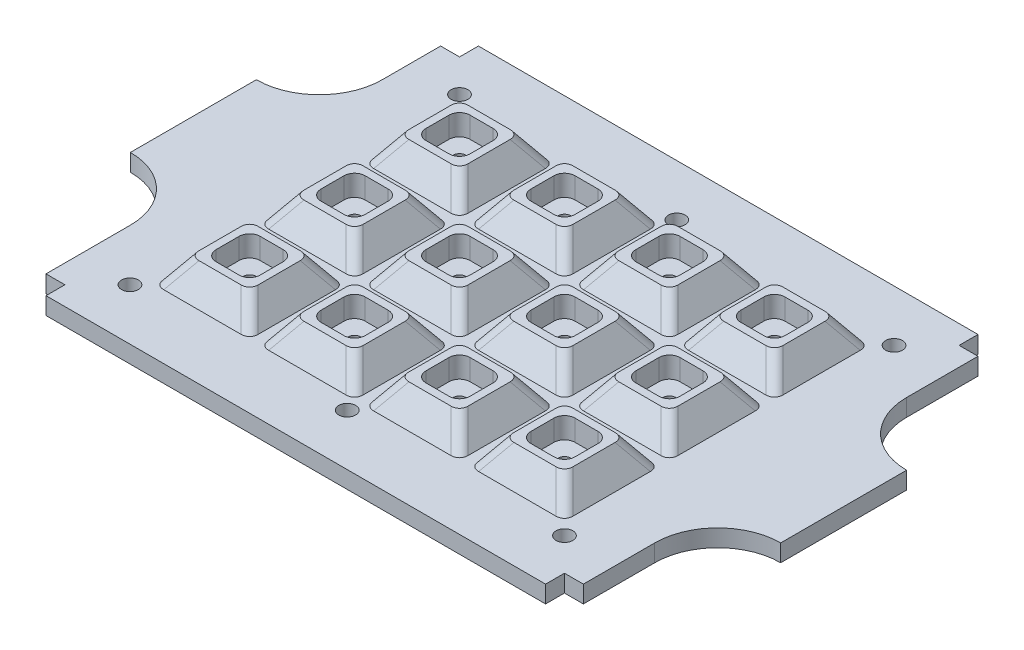
SolidWorks part; units mm, degrees
ref_plane "Front Plane" through (0, 0, 0) normal (0, 0, 1) x (1, 0, 0)
ref_plane "Top Plane" through (0, 0, 0) normal (0, 1, 0) x (1, 0, 0)
ref_plane "Right Plane" through (0, 0, 0) normal (1, 0, 0) x (0, 0, -1)
sketch "Sketch1" plane through (0, 0, 0) normal (0, 1, 0) x (1, 0, 0)
  line L1 (0, 0) -> (31.75, 0)
  line L2 (0, 0) -> (0, 31.75)
  line L3 (0, 31.75) -> (31.75, 31.75)
  line L4 (31.75, 0) -> (31.75, 31.75)
  dimension "D1" = 31.75
extrude "Boss-Extrude1" add sketch "Sketch1" along normal blind 2.0828
sketch "Sketch2" plane through (0, 2.0828, 0) normal (0, 1, 0) x (1, 0, 0)
  line L0 (21.59, 15.875) -> (31.75, 15.875) construction
  line L1 (10.16, 21.59) -> (21.59, 21.59)
  line L2 (10.16, 21.59) -> (10.16, 10.16)
  line L3 (10.16, 10.16) -> (21.59, 10.16)
  line L4 (21.59, 21.59) -> (21.59, 10.16)
  line L5 (31.75, 0) -> (31.75, 31.75) construction
  line L6 (15.875, 10.16) -> (15.875, 0) construction
  line L7 (0, 0) -> (31.75, 0) construction
  dimension "D1" = 11.43
extrude "Boss-Extrude2" add sketch "Sketch2" along normal blind 3.048 draft 35 contours L4 L3 L2 L1
sketch "Sketch3" plane through (0, 5.1308, 0) normal (0, 1, 0) x (1, 0, 0)
  line L0 (15.875, 18.542) -> (15.875, 21.59) construction
  line L1 (13.208, 18.542) -> (18.542, 18.542)
  line L2 (13.208, 18.542) -> (13.208, 13.208)
  line L3 (13.208, 13.208) -> (18.542, 13.208)
  line L4 (18.542, 18.542) -> (18.542, 13.208)
  line L5 (10.16, 21.59) -> (21.59, 21.59) construction
  line L6 (18.542, 15.875) -> (19.4558, 15.875) construction
  line L7 (19.4558, 19.4558) -> (19.4558, 12.2942) construction
  line L8 (18.542, 15.875) -> (19.4558, 15.875) construction
  dimension "D1" = 5.334
extrude "Cut-Extrude1" cut sketch "Sketch3" against normal blind 2.54
fillet "Fillet4" radius 1.27 4 edges at (13.208, 3.8608, -18.542) (13.208, 3.8608, -13.208) (18.542, 3.8608, -13.208) (18.542, 3.8608, -18.542)
sketch "Sketch4" plane through (0, 2.0828, 0) normal (0, 1, 0) x (1, 0, 0)
  line L0 (10.16, 21.59) -> (10.16, 31.75) construction
  line L1 (31.75, 31.75) -> (0, 31.75) construction
  line L2 (10.16, 10.16) -> (0, 10.16) construction
  line L3 (0, 31.75) -> (0, 0) construction
  line L6 (15.875, 31.75) -> (15.875, 0) construction
  line L7 (0, 0) -> (31.75, 0) construction
  line L8 (0, 15.875) -> (31.75, 15.875) construction
  line L9 (31.75, 0) -> (31.75, 31.75) construction
  line L10 (4.9361, 26.8139) -> (10.16, 21.59) construction
  circle A0 centre (4.9361, 26.8139) radius 1.524
  circle A1 centre (26.8139, 26.8139) radius 1.524
  circle A2 centre (26.8139, 4.9361) radius 1.524
  circle A3 centre (4.9361, 4.9361) radius 1.524
  dimension "D1" = 3.048
extrude "Cut-Extrude2" cut sketch "Sketch4" against normal through all
sketch "Sketch6" plane through (0, 2.0828, 0) normal (0, 1, 0) x (1, 0, 0)
  line L0 (15.875, 13.208) -> (15.875, 18.542) construction
  line L1 (0, 0) -> (2.286, 0)
  line L2 (0, 0) -> (0, 2.286)
  line L3 (0, 2.286) -> (2.286, 2.286)
  line L4 (2.286, 0) -> (2.286, 2.286)
  line L5 (14.478, 13.208) -> (17.272, 13.208) construction
  line L6 (17.272, 18.542) -> (14.478, 18.542) construction
  line L7 (13.208, 15.875) -> (18.542, 15.875) construction
  line L8 (13.208, 17.272) -> (13.208, 14.478) construction
  line L9 (18.542, 14.478) -> (18.542, 17.272) construction
  line L10 (31.75, 2.286) -> (29.464, 2.286)
  line L11 (29.464, 0) -> (29.464, 2.286)
  line L12 (31.75, 0) -> (29.464, 0)
  line L13 (31.75, 0) -> (31.75, 2.286)
  line L14 (0, 31.75) -> (2.286, 31.75)
  line L15 (0, 31.75) -> (0, 29.464)
  line L16 (0, 29.464) -> (2.286, 29.464)
  line L17 (2.286, 31.75) -> (2.286, 29.464)
  line L18 (31.75, 31.75) -> (31.75, 29.464)
  line L19 (31.75, 31.75) -> (29.464, 31.75)
  line L20 (29.464, 31.75) -> (29.464, 29.464)
  line L21 (31.75, 29.464) -> (29.464, 29.464)
  line L22 (31.75, 0) -> (29.464, 0)
  line L23 (31.75, 0) -> (31.75, 2.286)
  line L24 (31.75, 2.286) -> (29.464, 2.286)
  line L25 (29.464, 0) -> (29.464, 2.286)
  point P21 (15.875, 15.875)
  point P37 (15.875, 15.875)
  line M22 (0, 31.75) -> (0, 0)
  line M23 (0, 0) -> (31.75, 0)
  line M24 (31.75, 0) -> (31.75, 31.75)
  line M25 (31.75, 31.75) -> (0, 31.75)
  dimension "D1" = 2.286
  dimension "D2" = 4
extrude "Cut-Extrude3" cut sketch "Sketch6" against normal through all contours L17 L16 M25 M22 | L4 L3 M23 M22 | L21 L20 M24 M25 | L11 L10 L13 L12 region at (1.143, 2.0828, -1.143) region at (1.143, 2.0828, -30.607) region at (30.607, 2.0828, -30.607)
fillet "Fillet1" radius 1.27 4 edges at (11.2271, 3.6068, -11.2271) (20.5229, 3.6068, -11.2271) (20.5229, 3.6068, -20.5229) (11.2271, 3.6068, -20.5229)
sketch "Sketch7" plane through (0, 0, 0) normal (0, -1, 0) x (1, 0, 0)
  line L0 (15.875, 0) -> (15.875, -31.75) construction
  line L1 (2.286, 0) -> (29.464, 0) construction
  line L2 (29.464, -31.75) -> (2.286, -31.75) construction
  line L4 (22.225, -22.225) -> (9.525, -22.225)
  line L5 (22.225, -22.225) -> (22.225, -9.525)
  line L6 (22.225, -9.525) -> (9.525, -9.525)
  line L7 (9.525, -22.225) -> (9.525, -9.525)
  line L8 (22.225, -22.225) -> (9.525, -9.525) construction
  line L9 (22.225, -9.525) -> (9.525, -22.225) construction
  line L10 (31.75, -31.75) -> (0, -31.75)
  line L11 (31.75, -31.75) -> (31.75, 0)
  line L12 (31.75, 0) -> (0, 0)
  line L13 (0, -31.75) -> (0, 0)
  line L14 (31.75, -31.75) -> (0, 0) construction
  line L15 (31.75, 0) -> (0, -31.75) construction
  point P6 (15.875, -15.875)
  point P11 (15.875, -15.875)
  dimension "D1" = 12.7
extrude "Cut-Extrude4" cut sketch "Sketch7" against normal blind 2.54
pattern_linear "LPattern1" count 4 spacing 12.7 along (1, 0, 0) count 3 spacing 12.7 along (0, 0, -1) of bodies 107
ref_plane "Plane1" through (34.925, 0, 0) normal (-1, 0, 0) x (0, 0, 1)
sketch "Sketch8" plane through (0, 0, 0) normal (0, -1, 0) x (1, 0, 0)
  line L0 (2.413, -28.575) -> (9.525, -28.575) construction
  line L1 (2.413, -2.413) -> (67.437, -2.413)
  line L2 (2.413, -2.413) -> (2.413, -54.737)
  line L3 (2.413, -54.737) -> (67.437, -54.737)
  line L4 (67.437, -2.413) -> (67.437, -54.737)
  line L5 (9.525, -22.225) -> (9.525, -34.925) construction
  line L6 (34.925, -9.525) -> (34.925, -54.737) construction
  line L8 (10.033, -37.7702) -> (-5.207, -37.7702)
  line L9 (10.033, -37.7702) -> (10.033, -22.5302)
  line L10 (10.033, -22.5302) -> (-5.207, -22.5302)
  line L11 (-5.207, -37.7702) -> (-5.207, -22.5302)
  line L12 (10.033, -37.7702) -> (-5.207, -22.5302) construction
  line L13 (10.033, -22.5302) -> (-5.207, -37.7702) construction
  line L14 (59.817, -36.195) -> (75.057, -36.195)
  line L15 (59.817, -36.195) -> (59.817, -20.955)
  line L16 (59.817, -20.955) -> (75.057, -20.955)
  line L17 (75.057, -36.195) -> (75.057, -20.955)
  line L18 (59.817, -36.195) -> (75.057, -20.955) construction
  line L19 (59.817, -20.955) -> (75.057, -36.195) construction
  point P11 (2.413, -30.1502)
  point P16 (67.437, -28.575)
  line M5 (47.625, -9.525) -> (34.925, -9.525)
  line M6 (34.925, -9.525) -> (34.925, -22.225)
  line M7 (34.925, -22.225) -> (47.625, -22.225)
  line M8 (47.625, -22.225) -> (47.625, -9.525)
  dimension "D1" = 65.024
  dimension "D2" = 52.324
  dimension "D3" = 15.24
extrude "Boss-Extrude5" add sketch "Sketch8" against normal up to surface (2.0828 mm away) contours L15 L16 L4 L1 L2 L10 L9 L8 L3 L14 M5 M8 M7 M6 | L11 L8 L2 L10 | L15 L14 L17 L16 | L9 L8 L11 L10 region at (34.5846, 0, -29.195) region at (-1.397, 0, -30.1502) up to face at (15.875, 2.0828, -15.875)
fillet "Fillet5" radius 7.62 4 edges at (2.413, 1.0414, -22.5302) (67.437, 1.0414, -36.195) (2.413, 1.0414, -37.7702) (67.437, 1.0414, -20.955)
sketch "Sketch9" plane through (0, 2.0828, 0) normal (0, 1, 0) x (1, 0, 0)
  line L0 (15.875, 46.99) -> (15.875, 48.514) construction
  line L1 (11.2003, 46.99) -> (20.5497, 46.99) construction
  line L2 (15.875, 48.514) -> (8.636, 48.514) construction
  line L3 (8.636, 48.514) -> (8.636, 41.275) construction
  line L4 (8.636, 41.275) -> (10.16, 41.275) construction
  line L5 (10.16, 45.9497) -> (10.16, 36.6003) construction
  circle A0 centre (8.636, 48.514) radius 1.016
  dimension "D2" = 2.032
  dimension "D1" = 1.524
extrude "Cut-Extrude5" cut sketch "Sketch9" against normal through all
pattern_linear "LPattern2" count 3 spacing 26.289 along (1, 0, 0) count 2 spacing 39.878 along (0, 0, 1) of "Cut-Extrude5"
sketch "Sketch10" plane through (0, 2.0828, 0) normal (0, 1, 0) x (1, 0, 0)
  line L1 (2.413, 54.737) -> (4.699, 54.737)
  line L2 (2.413, 54.737) -> (2.413, 52.451)
  line L3 (2.413, 52.451) -> (4.699, 52.451)
  line L4 (4.699, 54.737) -> (4.699, 52.451)
  dimension "D1" = 2.286
extrude "Cut-Extrude6" cut sketch "Sketch10" against normal through all
pattern_linear "LPattern3" count 2 spacing 62.738 along (1, 0, 0) count 2 spacing 50.038 along (0, 0, 1) of "Cut-Extrude6"
sketch "Sketch12" plane through (0, 2.5908, 0) normal (0, 1, 0) x (1, 0, 0)
  line L0 (13.58, 43.57) -> (18.17, 38.98) construction
  line L1 (13.58, 38.98) -> (18.17, 43.57) construction
  arc A0 (14.478, 43.942) -> (13.208, 42.672) centre (14.478, 42.672) ccw construction
  arc A1 (17.272, 38.608) -> (18.542, 39.878) centre (17.272, 39.878) ccw construction
  arc A2 (13.208, 39.878) -> (14.478, 38.608) centre (14.478, 39.878) ccw construction
  arc A3 (18.542, 42.672) -> (17.272, 43.942) centre (17.272, 42.672) ccw construction
  circle A4 centre (15.875, 41.275) radius 0.762
extrude "Cut-Extrude7" cut sketch "Sketch12" against normal through all
pattern_linear "LPattern4" count 4 spacing 12.7 along (1, 0, 0) count 3 spacing 12.7 along (0, 0, 1) of "Cut-Extrude7"
